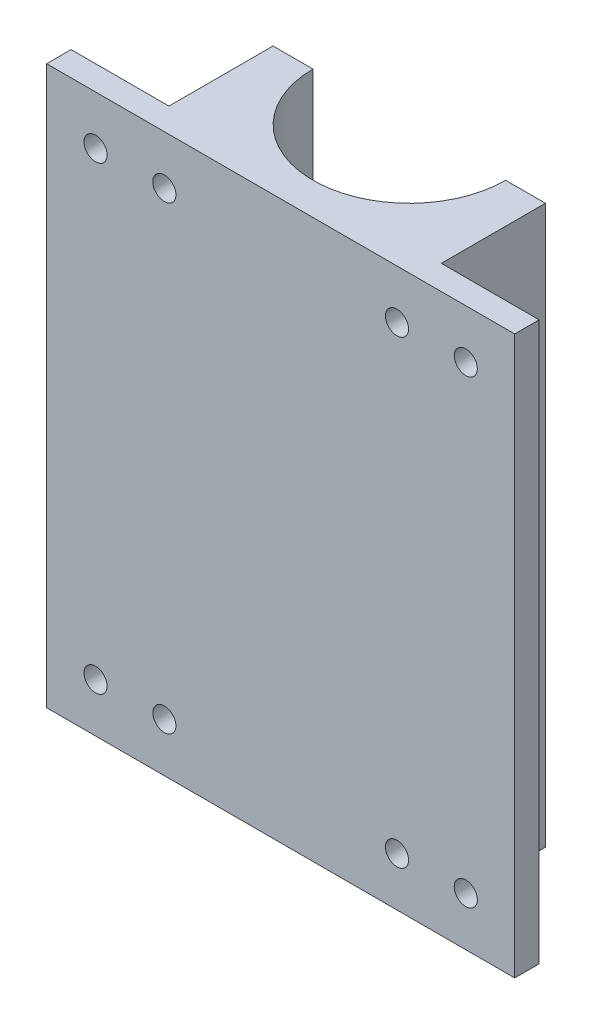
SolidWorks part; units mm, degrees
ref_plane "Front Plane" through (0, 0, 0) normal (0, 0, 1) x (1, 0, 0)
ref_plane "Top Plane" through (0, 0, 0) normal (0, 1, 0) x (1, 0, 0)
ref_plane "Right Plane" through (0, 0, 0) normal (1, 0, 0) x (0, 0, -1)
sketch "Sketch1" plane through (0, 0, 0) normal (0, 1, 0) x (1, 0, 0)
  line L1 (-23.8485, 17.6982) -> (36.9033, 17.6982)
  line L2 (-23.8485, 17.6982) -> (-23.8485, 14.5232)
  line L3 (-23.8485, 14.5232) -> (36.9033, 14.5232)
  line L4 (36.9033, 17.6982) -> (36.9033, 14.5232)
  line L6 (24.2033, 31.2048) -> (-11.1467, 31.2048)
  line L7 (24.2033, 31.2048) -> (24.2033, 17.6982)
  line L8 (24.2033, 17.6982) -> (-11.1467, 17.6982)
  line L9 (-11.1467, 31.2048) -> (-11.1467, 17.6982)
  line L10 (-5.958, 31.2048) -> (-5.658, 31.2048)
  line L11 (19.042, 31.2048) -> (18.742, 31.2048)
  line L12 (6.5283, 38.6577) -> (6.5283, -0.813) construction
  arc A2 (-5.958, 31.2048) -> (19.042, 31.2048) centre (6.542, 31.2048) ccw
  arc A3 (-5.658, 31.2048) -> (18.742, 31.2048) centre (6.542, 31.2048) ccw
  point P13 (0, 0)
  point P17 (0, 0)
  point P18 (0, 0)
  dimension "D4" = 5.1613
  dimension "D6" = 0.3
  dimension "D1" = 12.7018
  dimension "D3" = 5.1887
  dimension "D2" = 12.7
  dimension "D5" = 0.3
extrude "Boss-Extrude2" add sketch "Sketch1" along normal blind 72.39 contours L12 A2 L6 L9 L1 | L12 L1 L2 L3 | A2 L12 L8 L7 L6 | L8 L12 L3 L4 L1 region at (-8.6601, 0, -16.1107) region at (-6.0417, 0, -22.9226) region at (19.1064, 0, -22.9166) region at (21.7158, 0, -16.1107)
extrude "Boss-Extrude3" add sketch "Sketch1<16>" along normal blind 51.39 contours A2 L11 A3 L10
sketch "Sketch1<16>" plane through (0, 0, 0) normal (0, 1, 0) x (1, 0, 0) same geometry as "Sketch1"
hole_wizard "Ø3.0mm Dowel Hole1" positions "Sketch4" profile "Sketch5" hole size "Ø3.0" standard "ANSI Metric"
sketch "Sketch4" plane through (0, 0, -17.6982) normal (0, 0, -1) x (-1, 0, 0)
  line L0 (-24.2033, 72.39) -> (-36.9033, 72.39) construction
  line L1 (-36.9033, 72.39) -> (-36.9033, 0) construction
  line L2 (-24.2033, 0) -> (-36.9033, 0) construction
  line L3 (23.8485, 0) -> (11.1467, 0) construction
  line L4 (23.8485, 72.39) -> (23.8485, 0) construction
  line L5 (23.8485, 72.39) -> (11.1467, 72.39) construction
  point P0 (-30.5533, 66.04)
  point P2 (-30.5533, 6.35)
  point P4 (17.4985, 6.35)
  point P6 (17.4985, 66.04)
  point P15 (-30.5533, 0)
  dimension "D1" = 6.35
  dimension "D2" = 6.35
  dimension "D3" = 6.35
  dimension "D4" = 6.35
  dimension "D5" = 6.35
  dimension "D6" = 6.35
  dimension "D7" = 6.35
  dimension "D8" = 6.35
sketch "Sketch5" plane through (30.5533, 66.04, -17.6982) normal (1, 0, 0) x (0, 1, 0)
  line L0 (0, 0) -> (0, 10.9013)
  line L1 (0, 10.9013) -> (1.5, 10)
  line L2 (1.5, 10) -> (1.5, 0)
  line L5 (1.5, 0) -> (0, 0)
  line L10 (0, 10.9013) -> (-1.5, 10) construction
  line L11 (0, -6.35) -> (0, 107.95) construction
  dimension "Hole Dia." = 3
  dimension "Hole Depth" = 10
  dimension "Drill Angle" = 118
hole_wizard "Ø3.0mm Dowel Hole2" positions "Sketch10" profile "Sketch11" hole size "Ø3.0" standard "ANSI Metric"
sketch "Sketch10" plane through (0, 0, -31.2048) normal (0, 0, -1) x (-1, 0, 0)
  line L0 (-24.2033, 72.39) -> (-19.042, 72.39) construction
  line L1 (-24.2033, 72.39) -> (-24.2033, 0) construction
  line L2 (5.958, 72.39) -> (11.1467, 72.39) construction
  line L3 (11.1467, 72.39) -> (11.1467, 0) construction
  line L4 (-24.2033, 0) -> (-18.742, 0) construction
  line L5 (5.658, 0) -> (11.1467, 0) construction
  point P0 (-21.6233, 66.04)
  point P2 (-21.6233, 6.35)
  point P4 (8.5667, 6.35)
  point P6 (8.5667, 66.04)
  dimension "D1" = 6.35
  dimension "D2" = 2.58
  dimension "D3" = 6.35
  dimension "D4" = 2.58
  dimension "D5" = 6.35
  dimension "D6" = 2.58
  dimension "D7" = 6.35
  dimension "D8" = 2.58
sketch "Sketch11" plane through (21.6233, 66.04, -31.2048) normal (1, 0, 0) x (0, 1, 0)
  line L0 (0, 0) -> (0, 20.9013)
  line L1 (0, 20.9013) -> (1.5, 20)
  line L2 (1.5, 20) -> (1.5, 0)
  line L5 (1.5, 0) -> (0, 0)
  line L10 (0, 20.9013) -> (-1.5, 20) construction
  line L11 (0, -6.35) -> (0, 107.95) construction
  dimension "Hole Dia." = 3
  dimension "Hole Depth" = 20
  dimension "Drill Angle" = 118
